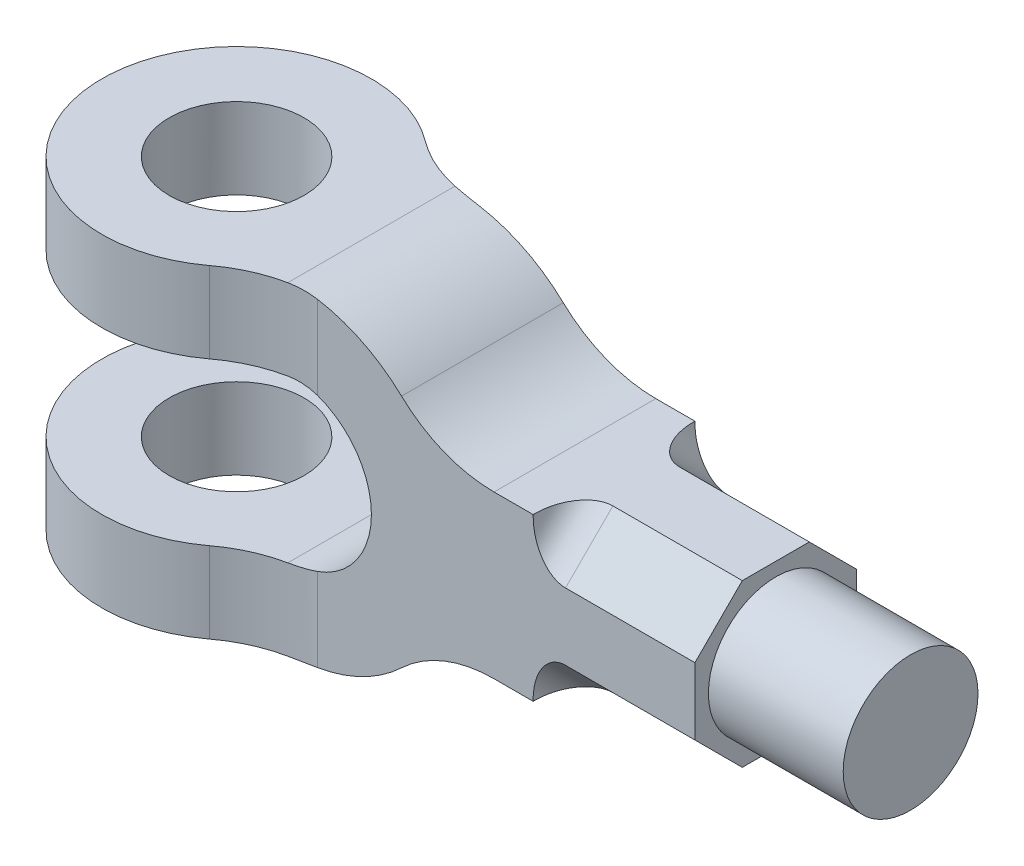
SolidWorks part; units mm, degrees
note: The reader was unsure of these and kept them because the rebuilt part matched: shared geometry of "Sketch2<2>".
ref_plane "Front Plane" through (0, 0, 0) normal (0, 0, 1) x (1, 0, 0)
ref_plane "Top Plane" through (0, 0, 0) normal (0, 1, 0) x (1, 0, 0)
ref_plane "Right Plane" through (0, 0, 0) normal (1, 0, 0) x (0, 0, -1)
sketch "Sketch1" plane through (0, 0, 0) normal (0, 0, 1) x (1, 0, 0)
  line L0 (-250, 60) -> (-250, 90)
  line L1 (0, 0) -> (-74.5017, 0)
  line L2 (0, 0) -> (0, 60)
  line L3 (0, 60) -> (-74.5017, 60)
  line L5 (-250, 90) -> (-150, 90)
  line L6 (-250, 60) -> (-150, 60)
  line L7 (-250, 0) -> (-250, -30)
  line L8 (-250, -30) -> (-150, -30)
  line L9 (0, 30) -> (-105.0246, 30) construction
  line L10 (-250, 0) -> (-150, 0)
  arc A0 (-150, 90) -> (-108.8191, 73.6364) centre (-150, 30) cw
  arc A1 (-108.8191, 73.6364) -> (-74.5017, 60) centre (-74.5017, 110) ccw
  arc A2 (-150, -30) -> (-108.8191, -13.6364) centre (-150, 30) ccw
  arc A3 (-108.8191, -13.6364) -> (-74.5017, 0) centre (-74.5017, -50) cw
  arc A4 (-150, 60) -> (-150, 0) centre (-150, 30) cw
  dimension "D2" = 60
  dimension "D5" = 50
  dimension "D1" = 60
  dimension "D4" = 100
  dimension "D6" = 30
  dimension "D7" = 100
extrude "Boss-Extrude1" add sketch "Sketch1" along normal blind 60
sketch "Sketch2" plane through (0, 90, 0) normal (0, 1, 0) x (1, 0, 0)
  line L0 (-250, -60) -> (-250, 0) construction
  circle A0 centre (-200, -30) radius 50
  circle A1 centre (-200, -30) radius 25
  point P5 (-250, -30)
  dimension "D1" = 100
  dimension "D2" = 50
extrude "Boss-Extrude2" add sketch "Sketch2" against normal up to surface (120 mm away) up to face at (-200, -30, 30)
extrude "Cut-Extrude1" cut sketch "Sketch2<2>" against normal through all contours A1
sketch "Sketch2<2>" plane through (0, 90, 0) normal (0, 1, 0) x (1, 0, 0) same geometry as "Sketch2"
sketch "Sketch3" plane through (0, 0, 60) normal (0, 0, 1) x (1, 0, 0)
  line L0 (-250, 60) -> (-250, 0)
  line L1 (-250, 0) -> (-150, 0)
  line L2 (-150, 0) -> (-150, 60)
  line L3 (-150, 60) -> (-250, 60)
extrude "Cut-Extrude2" cut sketch "Sketch3" against normal through all and the other way through all
sketch "Sketch4" plane through (0, 90, 0) normal (0, 1, 0) x (1, 0, 0)
  line L0 (-240, -60) -> (-250, -60) construction
  line L1 (-250, -60) -> (-250, 0) construction
  line L2 (-240, 0) -> (-250, 0) construction
  line L3 (-240, -60) -> (-250, -60)
  line L4 (-250, -60) -> (-250, 0)
  line L5 (-240, 0) -> (-250, 0)
  circle A1 centre (-200, -30) radius 25
  circle A2 centre (-200, -30) radius 25
  circle A3 centre (-200, -30) radius 50
  circle A4 centre (-200, -30) radius 50
  line M4 (-240, 0) -> (-250, 0)
  line M5 (-250, 0) -> (-250, -60)
  line M6 (-250, -60) -> (-240, -60)
  dimension "D1" = 0
  dimension "D2" = 0
extrude "Cut-Extrude3" cut sketch "Sketch4" against normal through all contours A4 M4 M5 | A4 L4 M6
sketch "Sketch5" plane through (0, 0, 0) normal (1, 0, 0) x (0, 0, -1)
  line L0 (-60, 60) -> (0, 60) construction
  line L1 (-42.4264, 60) -> (-60, 42.4264)
  line L2 (-60, 42.4264) -> (-60, 17.5736)
  line L3 (-60, 17.5736) -> (-42.4264, 0)
  line L4 (-42.4264, 0) -> (-17.5736, 0)
  line L5 (-17.5736, 0) -> (0, 17.5736)
  line L6 (0, 17.5736) -> (0, 42.4264)
  line L7 (0, 42.4264) -> (-17.5736, 60)
  line L8 (-17.5736, 60) -> (-42.4264, 60)
  line L9 (0, 0) -> (0, 60) construction
  line L10 (-60, 0) -> (0, 0) construction
  line L11 (-60, 0) -> (-60, 60) construction
  line L12 (0, 0) -> (0, 60)
  line L13 (-60, 0) -> (0, 0)
  line L14 (-60, 0) -> (-60, 60)
  line L15 (-60, 60) -> (0, 60)
  line M2 (0, 0) -> (0, 60)
  line M3 (0, 60) -> (-60, 60)
  line M4 (-60, 60) -> (-60, 0)
  line M5 (-60, 0) -> (0, 0)
extrude "Cut-Extrude4" cut sketch "Sketch5" against normal blind 60 contours L1 M3 M4 | L3 M4 M5 | L5 M5 M2 | L7 M2 M3
sketch "Sketch6" plane through (0, 0, 0) normal (1, 0, 0) x (0, 0, -1)
  line L0 (0, 17.5736) -> (0, 42.4264) construction
  line L1 (-42.4264, 60) -> (-17.5736, 60) construction
  circle A0 centre (-30, 30) radius 25
  point P5 (0, 30)
  point P8 (-30, 60)
  dimension "D1" = 50
extrude "Boss-Extrude3" add sketch "Sketch6" along normal blind 50
fillet "Fillet1" radius 12 4 edges at (-60, 51.2132, 51.2132) (-60, 51.2132, 8.7868) (-60, 8.7868, 51.2132) (-60, 8.7868, 8.7868)
fillet "Fillet2" radius 50 2 edges at (-160, 75, 0) (-160, 75, 60)
